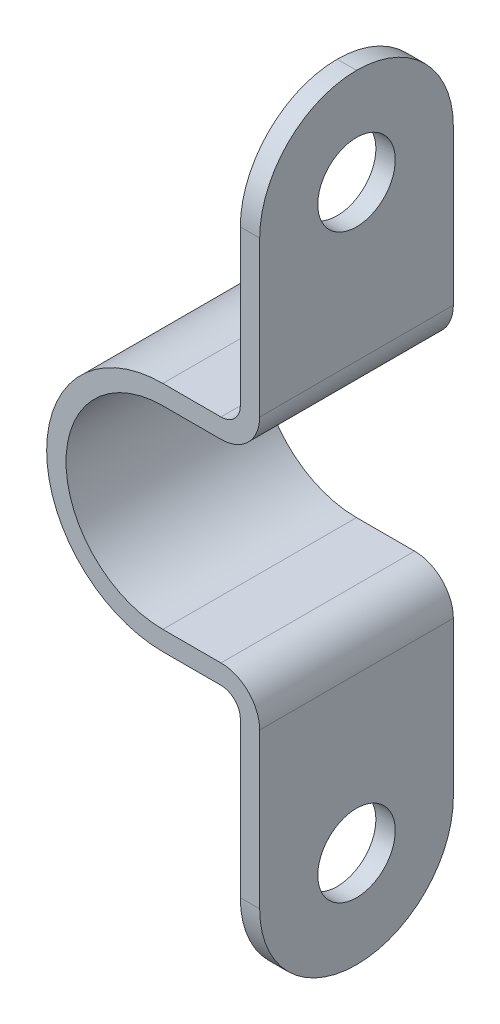
SolidWorks part; units mm, degrees
ref_plane "前视基准面" through (0, 0, 0) normal (0, 0, 1) x (1, 0, 0)
ref_plane "上视基准面" through (0, 0, 0) normal (0, 1, 0) x (1, 0, 0)
ref_plane "右视基准面" through (0, 0, 0) normal (1, 0, 0) x (0, 0, -1)
sketch "草图1" plane through (0, 0, 0) normal (0, 0, 1) x (1, 0, 0)
  line L0 (0, -5) -> (3, -5)
  line L1 (0, 5) -> (3, 5)
  line L2 (5, 7) -> (5, 20)
  line L3 (5, -7) -> (5, -20)
  arc A0 (0, 5) -> (0, -5) centre (0, 0) ccw
  arc A1 (5, -7) -> (3, -5) centre (3, -7) ccw
  arc A2 (3, 5) -> (5, 7) centre (3, 7) ccw
  dimension "D1" = 2
extrude "拉伸-薄壁1" add sketch "草图1" along normal blind 10 thin thin type one direction wall 1
fillet "圆角1" radius 5 4 edges at (4.5, 20, 10) (4.5, 20, 0) (4.5, -20, 10) (4.5, -20, 0)
sketch "草图2" plane through (4, 0, 0) normal (-1, 0, 0) x (0, 0, 1)
  circle A0 centre (5, -15) radius 2
  circle A1 centre (5, 15) radius 2
extrude "切除-拉伸1" cut sketch "草图2" against normal through all
